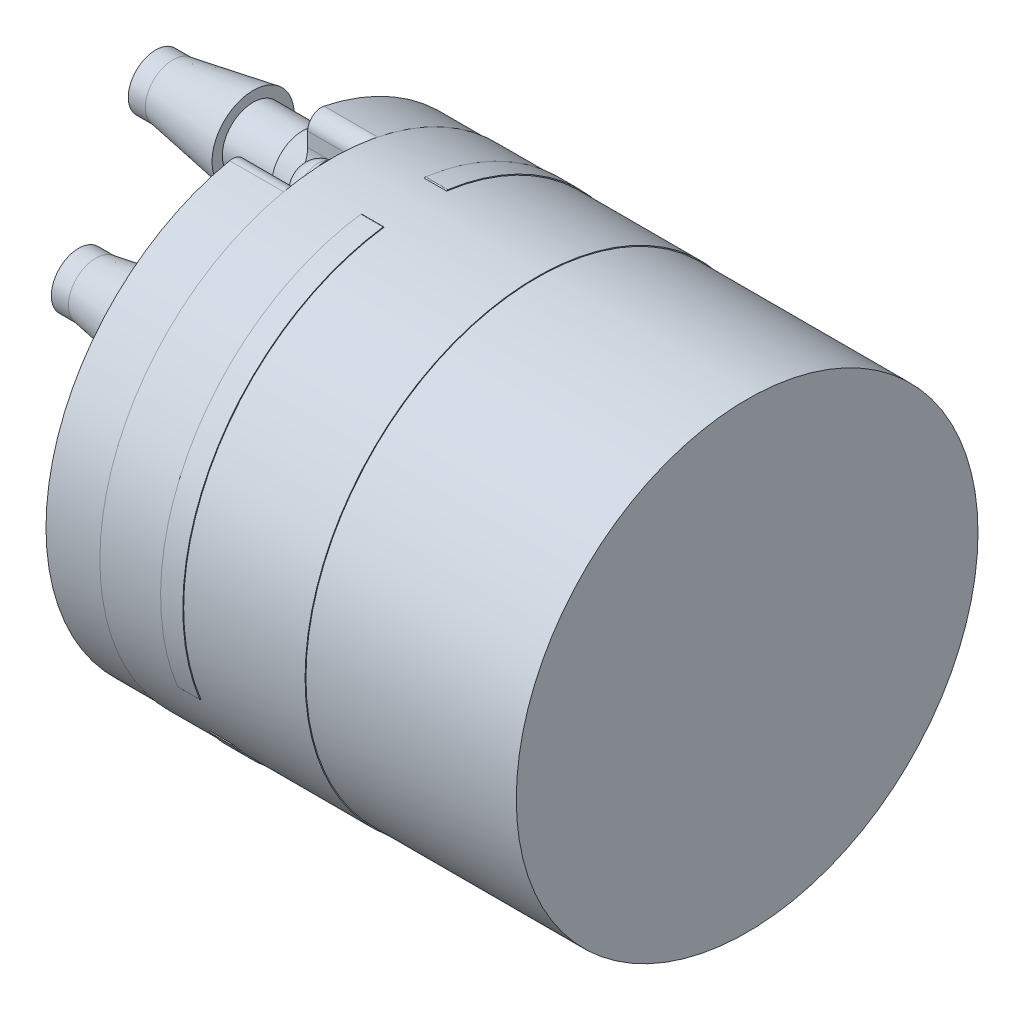
SolidWorks part; units mm, degrees
ref_plane "Front Plane" through (0, 0, 0) normal (0, 0, 1) x (1, 0, 0)
ref_plane "Top Plane" through (0, 0, 0) normal (0, 1, 0) x (1, 0, 0)
ref_plane "Right Plane" through (0, 0, 0) normal (1, 0, 0) x (0, 0, -1)
ref_plane "Base of Pump Plane" through (-31, 0, 0) normal (-1, 0, 0) x (0, 0, 1)
sketch "Pump OD Sketch" plane through (-31, 0, 0) normal (-1, 0, 0) x (0, 0, 1)
  circle A0 centre (0, 0) radius 13.5
  dimension "D1" = 27
extrude "Pump OD Extrude" add sketch "Pump OD Sketch" along normal blind 27.5 separate body
sketch "Pump Middle Sketch" plane through (-31, 0, 0) normal (-1, 0, 0) x (0, 0, 1)
  circle A0 centre (0, 0) radius 13.55
  circle A1 centre (0, 0) radius 13.5 construction
  dimension "D1" = 0.05
extrude "Pump Middle Extrude" add sketch "Pump Middle Sketch" along normal blind 12 from offset 12.3
sketch "Diaphragm Sketch" plane through (-55.3, 0, 0) normal (-1, 0, 0) x (0, 0, 1)
  line L0 (0, 0) -> (0, 12.2918) construction
  line L1 (-1.825, 12.2918) -> (1.825, 12.2918)
  line L2 (1.825, 12.2918) -> (1.825, 13.4081)
  line L3 (12.5243, -5.1236) -> (11.5575, -4.5654)
  line L4 (-1.825, 13.4081) -> (-1.825, 12.2918)
  line L5 (11.5575, -4.5654) -> (9.7325, -7.7264)
  line L6 (9.7325, -7.7264) -> (10.6993, -8.2846)
  line L7 (-10.6993, -8.2846) -> (-9.7325, -7.7264)
  line L8 (-9.7325, -7.7264) -> (-11.5575, -4.5654)
  line L9 (-11.5575, -4.5654) -> (-12.5243, -5.1236)
  arc A0 (-1.8934, 13.4676) -> (-12.6099, -5.0941) centre (0, 0) ccw
  circle A1 centre (0, 0) radius 13.55 construction
  arc A2 (1.825, 13.4081) -> (1.8934, 13.4676) centre (1.885, 13.4081) cw
  arc A3 (-1.8934, 13.4676) -> (-1.825, 13.4081) centre (-1.885, 13.4081) cw
  arc A4 (12.6099, -5.0941) -> (12.5243, -5.1236) centre (12.5543, -5.0716) cw
  arc A5 (10.6993, -8.2846) -> (10.7166, -8.3735) centre (10.6693, -8.3365) cw
  arc A6 (-10.7166, -8.3735) -> (-10.6993, -8.2846) centre (-10.6693, -8.3365) cw
  arc A7 (-12.5243, -5.1236) -> (-12.6099, -5.0941) centre (-12.5543, -5.0716) cw
  arc A8 (-10.7166, -8.3735) -> (10.7166, -8.3735) centre (0, 0) ccw
  arc A9 (12.6099, -5.0941) -> (1.8934, 13.4676) centre (0, 0) ccw
  point P32 (0, 0)
  dimension "D1" = 0.05
  dimension "D3" = 0.06
  dimension "D2" = 3.65
  dimension "D4" = 3
extrude "Diaphragm Extrude" add sketch "Diaphragm Sketch" against normal blind 1.3 from offset 3.6 offset against normal yes
sketch "Screw Pocket Sketch" plane through (-58.5, 0, 0) normal (-1, 0, 0) x (0, 0, 1)
  line L0 (0, 0) -> (0, 11.6) construction
  line L1 (-1.8, 11.6) -> (-1.8, 15.5376)
  line L2 (-1.8, 15.5376) -> (1.8, 15.5376)
  line L3 (1.8, 15.5376) -> (1.8, 11.6)
  arc A0 (-1.8, 11.6) -> (1.8, 11.6) centre (0, 11.6) ccw
  point P20 (0, 0)
  dimension "D1" = 3.6
  dimension "D2" = 11.6
extrude "Screw Pocket Cut" cut sketch "Screw Pocket Sketch" against normal up to surface (3.2 mm away) up to face at (-55.3, 0, 13.55)
fillet "Screw Pocket Fillet" radius 0.8 2 edges at (-56.9, 13.3795, -1.8) (-56.9, 13.3795, 1.8)
sketch "Scew Head Sketch" plane through (-55.3, 0, 0) normal (-1, 0, 0) x (0, 0, 1)
  circle A0 centre (0, 11.6) radius 1.3
  dimension "D1" = 2.6
extrude "Screw Head Extrude" add sketch "Scew Head Sketch" along normal blind 1.8
fillet "Screw Head Fillet" radius 1 1 edges at (-57.1, 11.6, 1.3)
sketch "Sketch10" plane through (-57.1, 0, 0) normal (-1, 0, 0) x (0, 0, 1)
  line L0 (0.15, 11.75) -> (0.15, 12.4)
  line L1 (-0.15, 10.8) -> (0.15, 10.8)
  line L2 (-0.15, 10.8) -> (-0.15, 11.45)
  line L3 (-0.15, 12.4) -> (0.15, 12.4)
  line L4 (0.15, 10.8) -> (0.15, 11.45)
  line L7 (-0.8, 11.75) -> (-0.15, 11.75)
  line L8 (-0.8, 11.75) -> (-0.8, 11.45)
  line L9 (-0.8, 11.45) -> (-0.15, 11.45)
  line L10 (0.8, 11.75) -> (0.8, 11.45)
  line L13 (0.15, 11.75) -> (0.8, 11.75)
  line L16 (0.15, 11.45) -> (0.8, 11.45)
  line L17 (-0.15, 11.75) -> (-0.15, 12.4)
  point P0 (0, 11.6)
  point P6 (0, 11.6)
  dimension "D1" = 0.3
  dimension "D2" = 1.6
extrude "Screw Drive Cut" cut sketch "Sketch10" against normal blind 1
sketch "Washer Sketch" plane through (-55.3, 0, 0) normal (-1, 0, 0) x (0, 0, 1)
  circle A0 centre (0, 11.6) radius 1.5818
extrude "Washer Extrude" add sketch "Washer Sketch" along normal blind 0.4
sketch "Center Nozzle Sketch" plane through (0, 0, 0) normal (0, 0, 1) x (1, 0, 0)
  line L0 (0, 0) -> (-76.9561, 0) construction
  line L1 (-70.0897, 1.6) -> (-69.0897, 1.6)
  line L2 (-58.5, 13.2141) -> (-58.5, -13.5) construction
  line L3 (-58.5, 2.7) -> (-61.5, 1.8)
  line L4 (-61.5, 1.8) -> (-64.3897, 1.8)
  line L5 (-64.3897, 1.8) -> (-64.3897, 2.4)
  line L6 (-69.0897, 1.6) -> (-64.3897, 2.4)
  line L7 (-70.0897, 1.6) -> (-70.0897, 1)
  line L8 (-70.0897, 1) -> (-58.5, 1)
  line L9 (-58.5, 1) -> (-58.5, 2.7)
  dimension "D1" = 3
  dimension "D2" = 5.7
  dimension "D3" = 1
  dimension "D4" = 5.4
  dimension "D5" = 3.6
  dimension "D6" = 4.8
  dimension "D7" = 3.2
  dimension "D8" = 2
  dimension "D9" = 2.8897
revolve "Center Nozzle Revolve" add sketch "Center Nozzle Sketch" angle 360 about L0
sketch "Nozzle Pattern Location Sketch" plane through (-58.5, 0, 0) normal (-1, 0, 0) x (0, 0, 1)
  line L0 (0, 0) -> (-4.5, 7.7942) construction
  line L1 (0, 0) -> (0, 4.3885) construction
  dimension "D1" = 30
  dimension "D2" = 9
pattern_linear "Nozzle LPattern" count 2 spacing 9 along (0, 0.866, -0.5) of "Center Nozzle Revolve"
